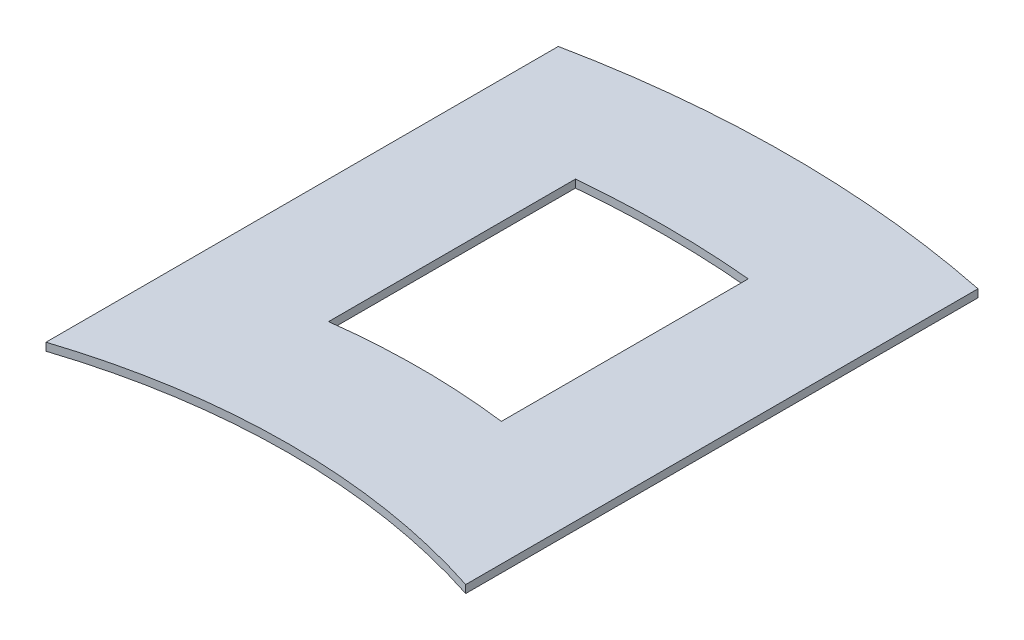
SolidWorks part; units mm, degrees
material "Copper"
ref_plane "Front" through (0, 0, 0) normal (0, 0, 1) x (1, 0, 0)
ref_plane "Top" through (0, 0, 0) normal (0, 1, 0) x (1, 0, 0)
ref_plane "Right" through (0, 0, 0) normal (1, 0, 0) x (0, 0, -1)
sketch "Sketch1" plane through (0, 0, 0) normal (0, 1, 0) x (1, 0, 0)
  line L0 (0, 0) -> (0, 4) construction
  line L2 (-1.4, 4) -> (-1.4, 0)
  line L3 (1.4, 4) -> (1.4, 0)
  line L4 (-3.4, 5.722) -> (-3.4, -2.5775)
  line L5 (3.4, 5.722) -> (3.4, -2.5775)
  arc A1 (-1.4, 0) -> (1.4, 0) centre (0, -10.9105) cw
  arc A2 (-1.4, 4) -> (1.4, 4) centre (0, -10.9345) cw
  arc A4 (-3.4, 5.722) -> (3.4, 5.722) centre (0, -10.9345) cw
  arc A5 (-3.4, -2.5775) -> (3.4, -2.5775) centre (0, -10.9105) cw construction
  arc A6 (-3.4, -2.5775) -> (3.4, -2.5775) centre (0, -13.0388) cw
  point P6 (0, 4)
  dimension "D1" = 4
  dimension "D2" = 11
  dimension "D4" = 15
  dimension "D6" = 11
  dimension "D3" = 2.8
  dimension "D5" = 2
extrude "Boss-Extrude1" add sketch "Sketch1" along normal blind 0.127
